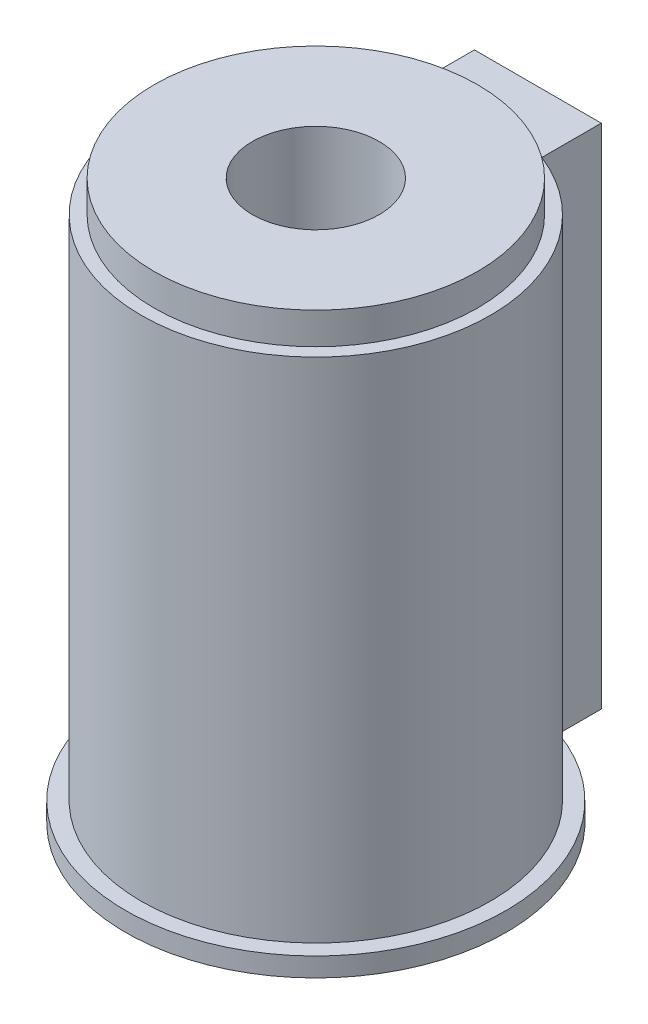
SolidWorks part; units mm, degrees
ref_plane "Alzado" through (0, 0, 0) normal (0, 0, 1) x (1, 0, 0)
ref_plane "Planta" through (0, 0, 0) normal (0, 1, 0) x (1, 0, 0)
ref_plane "Vista lateral" through (0, 0, 0) normal (1, 0, 0) x (0, 0, -1)
sketch "Croquis1" plane through (0, 0, 0) normal (0, 1, 0) x (1, 0, 0)
  line L0 (-100, 350) -> (-100, 256.1738)
  line L1 (-100, 350) -> (100, 350)
  line L2 (100, 350) -> (100, 256.1738)
  line L3 (0, 0) -> (0, 350) construction
  circle A0 centre (0, 0) radius 275
  dimension "D1" = 550
  dimension "D2" = 350
  dimension "D3" = 200
extrude "Saliente-Extruir1" add sketch "Croquis1" along normal blind 800 contours A0 region at (0, 0, 0)
extrude "Saliente-Extruir2" add sketch "Croquis1<3>" along normal blind 800 contours A0 L3 L1 L0 | L3 A0 L2 L1 region at (-51.9184, 0, -309.2145) region at (51.9184, 0, -309.2145)
sketch "Croquis1<3>" plane through (0, 0, 0) normal (0, 1, 0) x (1, 0, 0) same geometry as "Croquis1"
sketch "Croquis2" plane through (0, 0, 0) normal (0, -1, 0) x (1, 0, 0)
  circle A0 centre (0, 0) radius 300
  dimension "D1" = 600
extrude "Saliente-Extruir3" add sketch "Croquis2" along normal blind 30
sketch "Croquis7" plane through (0, 800, 0) normal (0, 1, 0) x (1, 0, 0)
  circle A0 centre (0, 0) radius 255
  dimension "D1" = 510
extrude "Saliente-Extruir4" add sketch "Croquis7" along normal blind 50
sketch "Croquis8" plane through (0, 850, 0) normal (0, 1, 0) x (1, 0, 0)
  circle A0 centre (0, 0) radius 100
  dimension "D1" = 200
extrude "Cortar-Extruir1" cut sketch "Croquis8" against normal through all both and the other way through all
